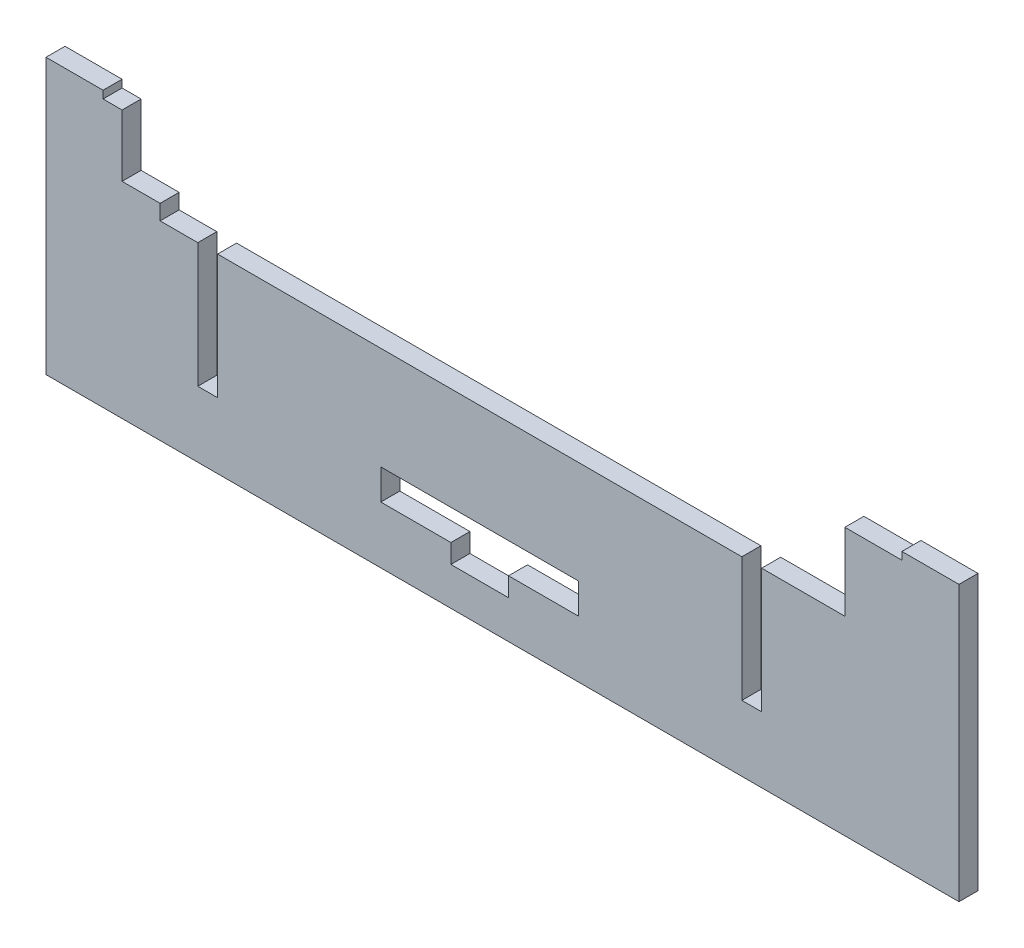
SolidWorks part; units mm, degrees
material "Acrylic (Medium-high impact)"
ref_plane "Front Plane" through (0, 0, 0) normal (0, 0, 1) x (1, 0, 0)
ref_plane "Top Plane" through (0, 0, 0) normal (0, 1, 0) x (1, 0, 0)
ref_plane "Right Plane" through (0, 0, 0) normal (1, 0, 0) x (0, 0, -1)
sketch "Sketch1" plane through (0, 0, 0) normal (0, 0, 1) x (1, 0, 0)
  line L0 (0, 0) -> (240, 0)
  line L2 (210, 54) -> (210, 50)
  line L3 (240, 0) -> (240, 72.25)
  line L4 (30, 50) -> (30, 54)
  line L5 (30, 54) -> (20, 54)
  line L6 (240, 72.25) -> (225, 72.25)
  line L7 (225, 72.25) -> (225, 70.25)
  line L8 (225, 70.25) -> (210, 70.25)
  line L9 (210, 70.25) -> (210, 54)
  line L10 (210, 50) -> (30, 50)
  line L11 (20, 54) -> (20, 70.25)
  line L12 (20, 70.25) -> (15, 70.25)
  line L13 (15, 70.25) -> (15, 72.25)
  line L14 (15, 72.25) -> (0, 72.25)
  line L17 (0, 72.25) -> (0, 0)
  dimension "D1" = 20
  dimension "D2" = 30
  dimension "D3" = 240
  dimension "D4" = 15
  dimension "D5" = 2
  dimension "D6" = 22.25
  dimension "D7" = 50
  dimension "D8" = 10
  dimension "D9" = 4
extrude "Boss-Extrude1" add sketch "Sketch1" along normal blind 5
ref_plane "Plane1" through (0, 50, 0) normal (0, 1, 0) x (-1, 0, 0)
extrude "Cut-Extrude6" cut sketch "Sketch7" along normal blind 32.7
sketch "Sketch7" plane through (76.9623, 50, 79.9822) normal (0, -1, 0) x (0.2993, 0, -0.9541)
  line L0 (89.5769, 88.4037) -> (121.0271, 78.537)
  line L1 (89.5769, 88.4037) -> (88.0203, 83.4422)
  line L2 (121.0271, 78.537) -> (119.4705, 73.5754)
  line L3 (88.0203, 83.4422) -> (119.4705, 73.5754)
  line L4 (88.7986, 85.9229) -> (120.2488, 76.0562) construction
  line L5 (120.3477, 133.1166) -> (125.1184, 131.6199) construction
  line L6 (48.5061, -95.8785) -> (120.3477, 133.1166) construction
  dimension "D1" = 54.4736
  dimension "D2" = 5.2
extrude "Cut-Extrude7" cut sketch "Sketch8" along normal blind 32.7
sketch "Sketch8" plane through (151.0641, 50, -36.8163) normal (0, -1, 0) x (-0.2993, 0, 0.9541)
  line L0 (48.2811, 101.3593) -> (121.0271, 78.537)
  line L1 (48.2811, 101.3593) -> (46.7245, 96.3977)
  line L2 (121.0271, 78.537) -> (119.4705, 73.5754)
  line L3 (46.7245, 96.3977) -> (119.4705, 73.5754)
  line L4 (85.1184, 131.6199) -> (13.2768, -97.3752) construction
  line L5 (120.2488, 76.0562) -> (47.5028, 98.8785) construction
  line L6 (85.1184, 131.6199) -> (80.3477, 133.1166) construction
  dimension "D1" = 42.5
  dimension "D2" = 5.2
extrude "Cut-Extrude8" cut sketch "Sketch9" against normal blind 50
sketch "Sketch9" plane through (179.8229, 98.1669, 0) normal (0, 0, -1) x (-1, 0, 0)
  line L0 (91.8097, -83.1669) -> (73.3847, -83.1669)
  line L1 (39.8097, -83.1669) -> (39.8097, -75.1669)
  line L2 (39.8097, -75.1669) -> (91.8097, -75.1669)
  line L3 (91.8097, -75.1669) -> (91.8097, -83.1669)
  line L4 (58.2347, -88.1669) -> (58.2347, -83.1669)
  line L5 (65.8097, -75.1669) -> (65.8097, -88.1669) construction
  line L7 (-60.1771, -98.1669) -> (-60.1771, -25.9169) construction
  line L9 (73.3847, -83.1669) -> (73.3847, -88.1669)
  line L10 (58.2347, -88.1669) -> (73.3847, -88.1669)
  line L12 (179.8229, -98.1669) -> (-60.1771, -98.1669) construction
  line L13 (58.2347, -83.1669) -> (39.8097, -83.1669)
  dimension "D1" = 8
  dimension "D2" = 125.9868
  dimension "D4" = 10
  dimension "D5" = 15.15
  dimension "D6" = 5
  dimension "D7" = 52
